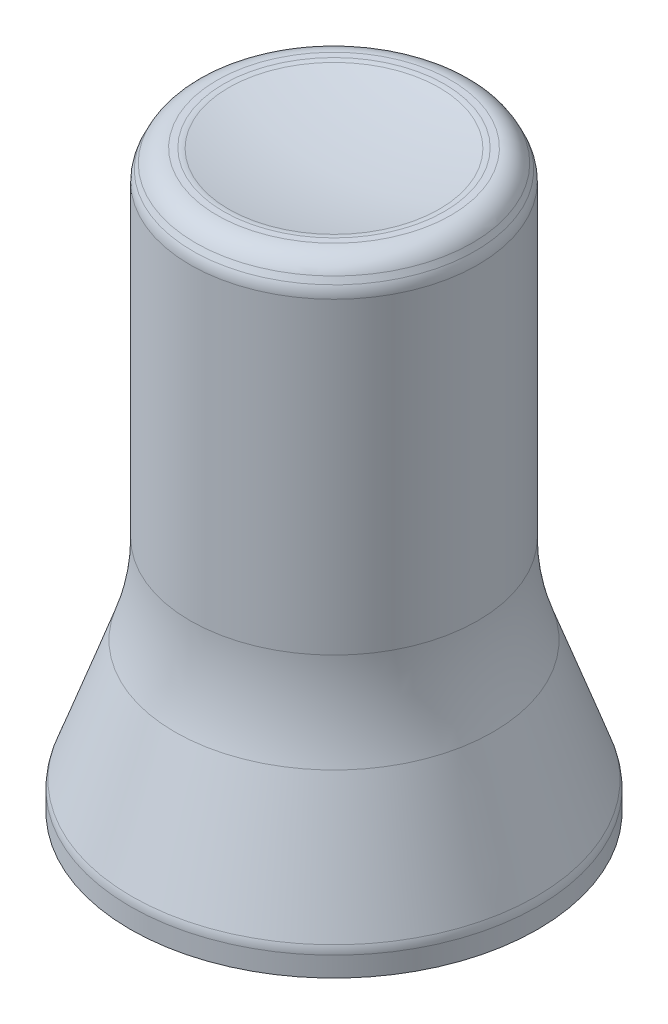
SolidWorks part; units mm, degrees
ref_plane "Front Plane" through (0, 0, 0) normal (0, 0, 1) x (1, 0, 0)
ref_plane "Top Plane" through (0, 0, 0) normal (0, 1, 0) x (1, 0, 0)
ref_plane "Right Plane" through (0, 0, 0) normal (1, 0, 0) x (0, 0, -1)
sketch "Sketch1" plane through (0, 0, 0) normal (0, 0, 1) x (1, 0, 0)
  line L0 (0, 0) -> (8.5, 0)
  line L1 (8.5, 0) -> (8.5, 1)
  line L2 (8.5, 1) -> (6, 8)
  line L3 (6, 8) -> (6, 23)
  line L4 (6, 23) -> (5.5, 24)
  line L5 (5.5, 24) -> (4.5, 24)
  line L6 (4.5, 24) -> (2.2778, 23.5) construction
  line L7 (0, 23.5) -> (0, 0) construction
  line L8 (0, 0) -> (0, 23.5)
  line L9 (2.2778, 23.5) -> (0, 23.5) construction
  spline S0 degree 2 poles (4.5, 24) (2.2778, 23.5) (0, 23.5) knots 0 0 0 1 1 1
  dimension "D1" = 24
  dimension "D2" = 6
  dimension "D3" = 1
  dimension "D4" = 8
  dimension "D5" = 1
  dimension "D6" = 0.5
  dimension "D7" = 0.5
  dimension "D8" = 1
  dimension "D9" = 8.5
  dimension "D10" = 6
revolve "Revolve1" add sketch "Sketch1" angle 360 about L7
fillet "Fillet1" radius 11 1 edges at (-6, 8, 0)
fillet "Fillet2" radius 1 4 edges at (-4.5, 24, 0) (-5.5, 24, 0) (-6, 23, 0) (-8.5, 1, 0)
sketch "Sketch3" plane through (0, 0, 0) normal (0, 0, 1) x (1, 0, 0)
  line L0 (0, 0) -> (3.875, 0)
  line L1 (-8.5, 0) -> (8.5, 0) construction
  line L2 (3.875, 0) -> (3.875, 6.5)
  line L3 (3.875, 6.5) -> (3.05, 7.325)
  line L4 (3.05, 7.325) -> (3.05, 17.75)
  line L5 (3.05, 17.75) -> (0, 17.75)
  line L6 (0, 17.75) -> (0, 0)
  dimension "D1" = 17.75
  dimension "D2" = 3.875
  dimension "D3" = 45
  dimension "D4" = 3.05
  dimension "D5" = 6.5
revolve "Cut-Revolve1" cut sketch "Sketch3" angle 360 about L6
ref_plane "Plane1" through (0, 7.325, 0) normal (0, 1, 0) x (1, 0, 0)
sketch "Sketch4" plane through (0, 17.75, 0) normal (0, -1, 0) x (1, 0, 0)
  line L0 (-2.6557, 1.5) -> (2.6557, 1.5)
  line L5 (-999.8551, -3) -> (49000.1449, -3) construction
  arc A7 (-0.1, -3.0484) -> (0.1, -3.0484) centre (0, 0) ccw
  arc A9 (0.1, -3.0484) -> (-0.1, -3.0484) centre (0, -3.05) ccw
  arc A10 (2.6557, 1.5) -> (-2.6557, 1.5) centre (0, 0) ccw
  circle A11 centre (0, 0) radius 3.05 construction
  point P1 (-1.8297, 1.5)
  point P10 (0, 0)
  point P11 (0, 0)
  dimension "D1" = 3
  dimension "D3" = 0.2
  dimension "D2" = 4.5
extrude "Boss-Extrude1" add sketch "Sketch4" along normal up to surface (10.425 mm away) up to plane "Plane1"
chamfer "Chamfer1" distance 0.35 angle 45 1 edges at (0, 7.325, 1.5)
